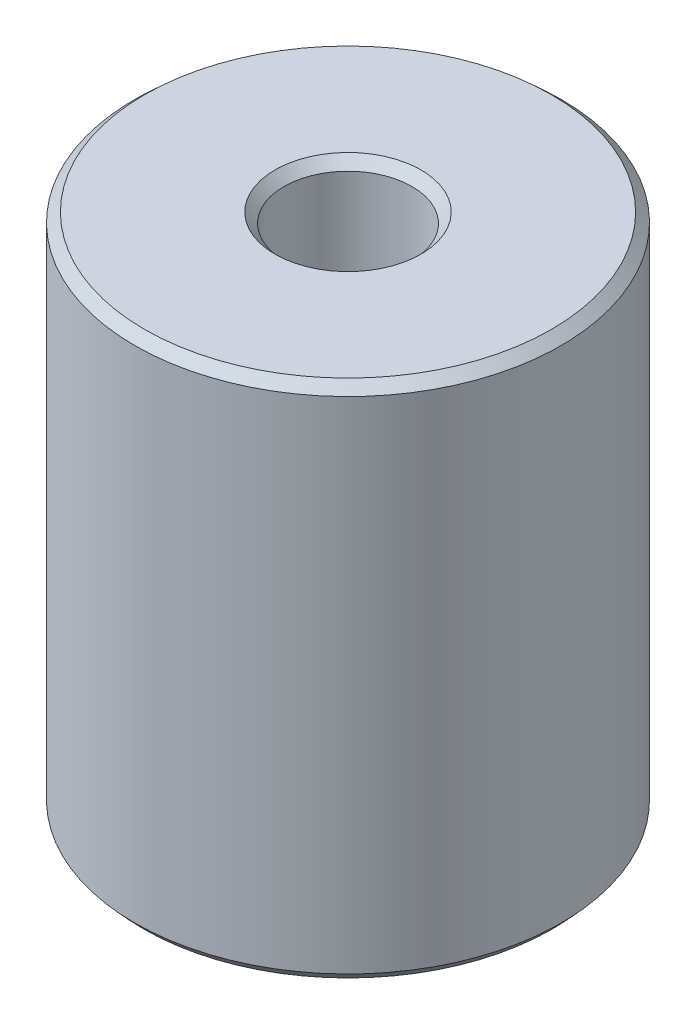
SolidWorks part; units mm, degrees
ref_plane "Front Plane" through (0, 0, 0) normal (0, 0, 1) x (1, 0, 0)
ref_plane "Top Plane" through (0, 0, 0) normal (0, 1, 0) x (1, 0, 0)
ref_plane "Right Plane" through (0, 0, 0) normal (1, 0, 0) x (0, 0, -1)
sketch "Sketch1" plane through (0, 0, 0) normal (0, 1, 0) x (1, 0, 0)
  circle A0 centre (0, 0) radius 5
  dimension "SLEEVE_OD" = 10
extrude "Boss-Extrude1" add sketch "Sketch1" along normal blind 12.1699
sketch "Sketch2" plane through (0, 0, 0) normal (0, 1, 0) x (1, 0, 0)
  circle A0 centre (0, 0) radius 1.5004
  dimension "BORE_D" = 3.0008
extrude "Cut-Extrude1" cut sketch "Sketch2" along normal through all
chamfer "Chamfer1" distance 0.2119 angle 47.452 4 edges at (0, 12.1699, 1.5004) (0, 0, 1.5004) (0, 0, 5) (0, 12.1699, 5) first distance on face at (0, 12.1699, 1.5004) first distance on face at (0, 0, 1.5004) first distance on face at (0, 12.1699, 5)
